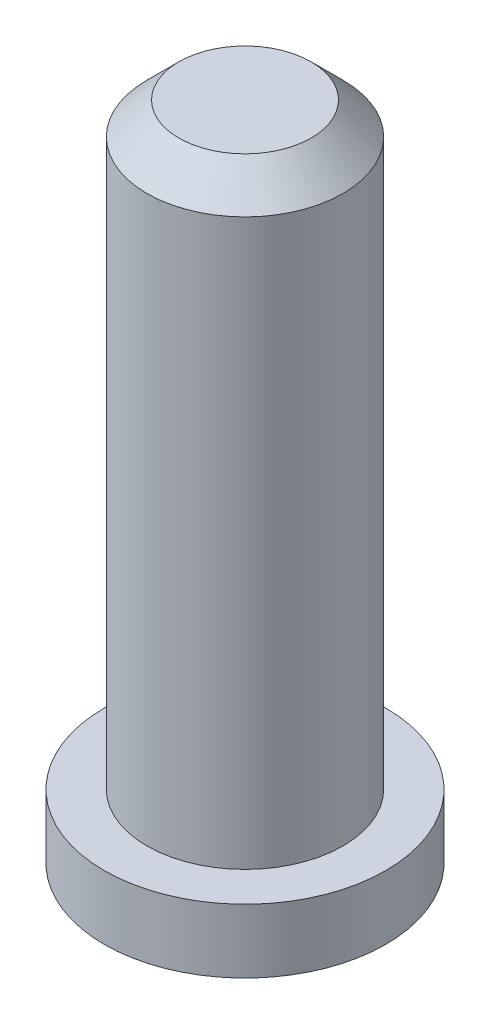
SolidWorks part; units mm, degrees
ref_plane "Front Plane" through (0, 0, 0) normal (0, 0, 1) x (1, 0, 0)
ref_plane "Top Plane" through (0, 0, 0) normal (0, 1, 0) x (1, 0, 0)
ref_plane "Right Plane" through (0, 0, 0) normal (1, 0, 0) x (0, 0, -1)
sketch "Sketch1" plane through (0, 0, 0) normal (0, 0, 1) x (1, 0, 0)
  line L0 (0, 0) -> (0, 15.5) construction
  line L1 (0, 15.5) -> (2.3, 15.5)
  line L2 (2.3, 15.5) -> (2.3, 1.5)
  line L3 (2.3, 1.5) -> (3.3, 1.5)
  line L4 (3.3, 1.5) -> (3.3, 0)
  line L5 (3.3, 0) -> (0, 0)
  line L6 (0, 0) -> (0, 15.5)
  dimension "D1" = 2.3
  dimension "D2" = 1.5
  dimension "D3" = 1
  dimension "D4" = 14
revolve "Revolve1" add sketch "Sketch1" angle 360 about L0
chamfer "Chamfer1" distance 0.75 angle 45 1 edges at (0, 15.5, -2.3)
